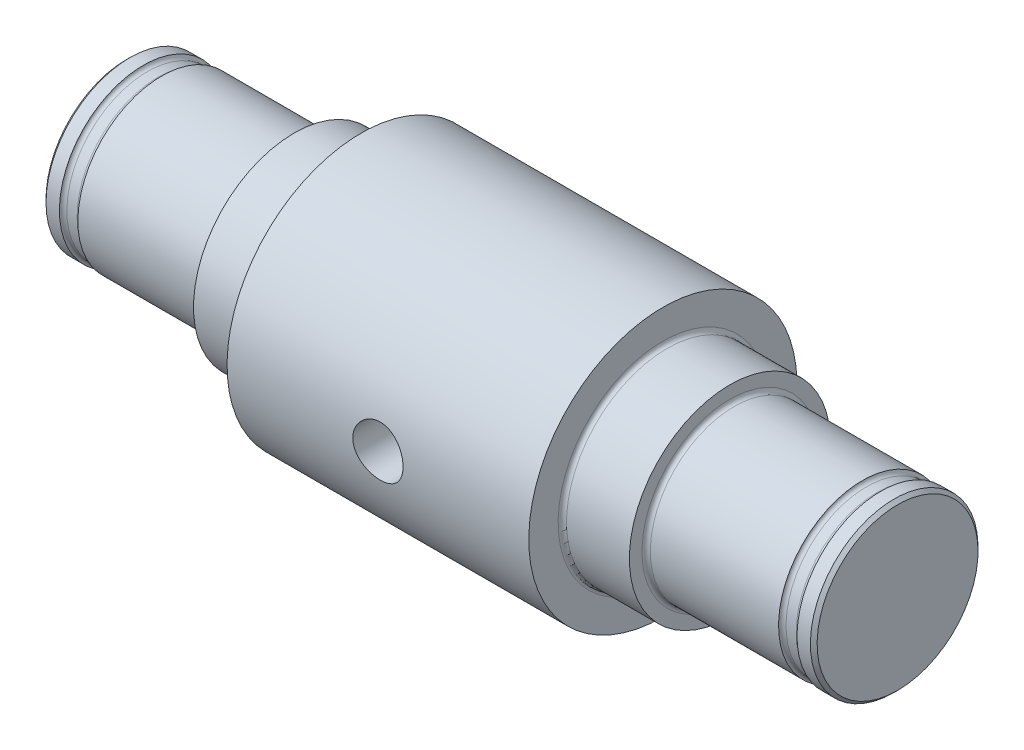
SolidWorks part; units mm, degrees
material "AISI 316 Annealed Stainless Steel Bar (SS)"
ref_plane "Front Plane" through (0, 0, 0) normal (0, 0, 1) x (1, 0, 0)
ref_plane "Top Plane" through (0, 0, 0) normal (0, 1, 0) x (1, 0, 0)
ref_plane "Right Plane" through (0, 0, 0) normal (1, 0, 0) x (0, 0, -1)
sketch "Sketch1" plane through (0, 0, 0) normal (0, 0, 1) x (1, 0, 0)
  line L0 (-55.3257, 0) -> (-23, 0) construction
  line L1 (55, 0) -> (-55, 0) construction
  line L2 (0, -44.7868) -> (0, 44.7868) construction
  line L4 (-23, 0) -> (-23, 5)
  line L6 (23, 0) -> (23, 5)
  line L7 (-23, 5) -> (-22, 5)
  line L8 (-13, 5) -> (-13, 6)
  line L9 (23, 0) -> (41.1493, 0) construction
  line L10 (-13, 6) -> (-9, 6)
  line L11 (-9, 6) -> (-9, 8)
  line L12 (-9, 8) -> (9, 8)
  line L13 (9, 8) -> (9, 6)
  line L14 (9, 6) -> (13, 6)
  line L15 (13, 6) -> (13, 5)
  line L16 (13, 5) -> (20.9, 5)
  line L17 (-23, 0) -> (23, 0)
  line L18 (-22, 5) -> (-22, 4.8)
  line L19 (-22, 4.8) -> (-20.9, 4.8)
  line L20 (-20.9, 4.8) -> (-20.9, 5)
  line L21 (20.9, 5) -> (20.9, 4.8)
  line L22 (20.9, 4.8) -> (22, 4.8)
  line L23 (22, 4.8) -> (22, 5)
  line L24 (-20.9, 5) -> (-13, 5)
  line L25 (22, 5) -> (23, 5)
  point P5 (0, 2.5)
  point P20 (0, 8)
  dimension "D1" = 4
  dimension "D2" = 5
  dimension "D3" = 18
  dimension "D4" = 9
  dimension "D5" = 9
  dimension "D6" = 6
  dimension "D7" = 8
  dimension "D8" = 4
  dimension "D9" = 1
  dimension "D10" = 1
  dimension "D11" = 1.1
  dimension "D12" = 1.1
  dimension "D13" = 4.8
  dimension "D14" = 0.2
revolve "Revolve1" add sketch "Sketch1" angle 360 about L0
ref_plane "Plane1" through (0, 0, 8) normal (0, 0, 1) x (1, 0, 0)
sketch "Sketch2" plane through (0, 0, 8) normal (0, 0, 1) x (1, 0, 0)
  line L0 (55, 0) -> (-55, 0) construction
  line L4 (0, -44.7868) -> (0, 44.7868) construction
  circle A0 centre (0, 0) radius 1.5
  dimension "D1" = 3
extrude "Cut-Extrude1" cut sketch "Sketch2" against normal through all
fillet "Fillet2" radius 0.25 4 edges at (-20.9, -4.8, 0) (-22, -4.8, 0) (22, -4.8, 0) (20.9, -4.8, 0)
fillet "Fillet3" radius 0.25 4 edges at (-13, -5, 0) (-9, -6, 0) (13, -5, 0) (9, -6, 0)
chamfer "Chamfer1" distance 0.2 angle 45 2 edges at (23, -5, 0) (-23, -5, 0)
